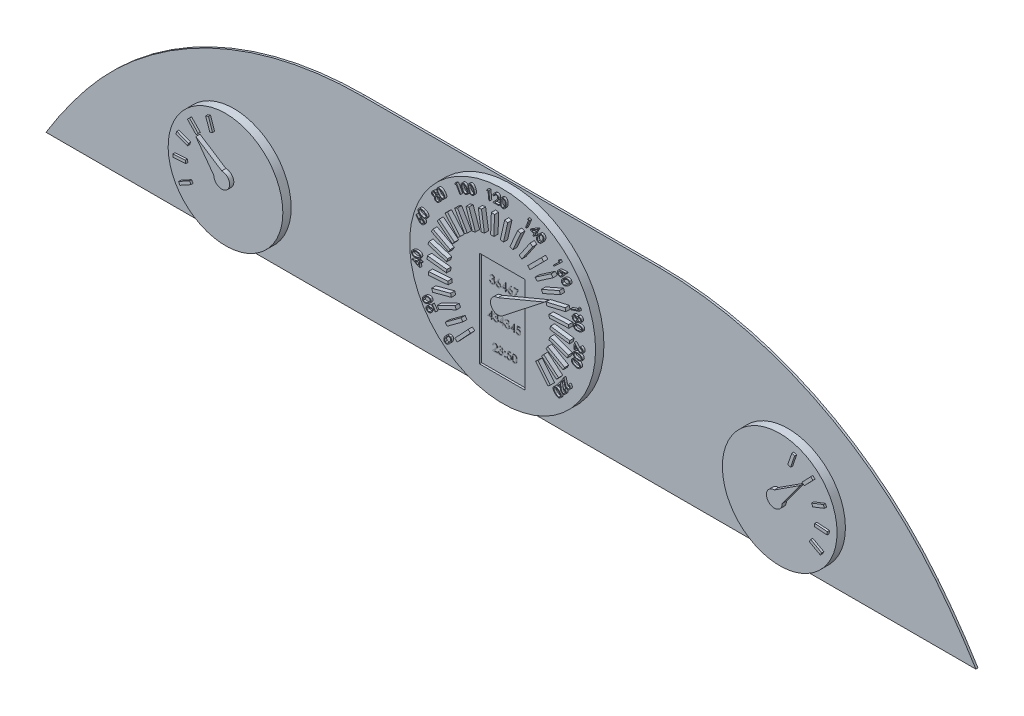
SolidWorks part; units mm, degrees
ref_plane "Front Plane" through (0, 0, 0) normal (0, 0, 1) x (1, 0, 0)
ref_plane "Top Plane" through (0, 0, 0) normal (0, 1, 0) x (1, 0, 0)
ref_plane "Right Plane" through (0, 0, 0) normal (1, 0, 0) x (0, 0, -1)
sketch "Sketch1" plane through (0, 0, 0) normal (0, 0, 1) x (1, 0, 0)
  line L1 (199.1432, -963.9827) -> (678.9972, -963.9827)
  line L2 (199.1432, -963.9827) -> (199.1432, -873.2403)
  line L3 (199.1432, -873.2403) -> (678.9972, -873.2403)
  line L4 (678.9972, -963.9827) -> (678.9972, -873.2403)
extrude "Boss-Extrude1" add sketch "Sketch1" along normal blind 1 contours L3 L4 L1 L2
sketch "Sketch2" plane through (0, 0, 1) normal (0, 0, 1) x (1, 0, 0)
  line L0 (439.0702, -790.2911) -> (439.0702, -1065.0749) construction
  circle A0 centre (439.0702, -918.6115) radius 44.5361
  circle A1 centre (571.7856, -936.6046) radius 27.4658
  circle A2 centre (306.3549, -936.6046) radius 27.4658
  point P6 (571.7856, -936.6046)
extrude "Boss-Extrude2" add sketch "Sketch2" along normal blind 4
sketch "Sketch3" plane through (0, 0, 5) normal (0, 0, 1) x (1, 0, 0)
  line L0 (424.5856, -938.6214) -> (425.708, -939.669)
  line L1 (424.5856, -938.6214) -> (418.2025, -945.4605)
  line L2 (425.708, -939.669) -> (419.3249, -946.5081)
  line L3 (418.2025, -945.4605) -> (419.3249, -946.5081)
  line L4 (421.1246, -935.5866) -> (422.0331, -936.8242)
  line L5 (422.0331, -936.8242) -> (414.4919, -942.3603)
  line L6 (421.1246, -935.5866) -> (413.5834, -941.1227)
  line L7 (413.5834, -941.1227) -> (414.4919, -942.3603)
  line L8 (418.2867, -931.9624) -> (418.9498, -933.3471)
  line L9 (418.9498, -933.3471) -> (410.5124, -937.3878)
  line L10 (418.2867, -931.9624) -> (409.8493, -936.0031)
  line L11 (409.8493, -936.0031) -> (410.5124, -937.3878)
  line L12 (416.1705, -927.8745) -> (416.5652, -929.3582)
  line L13 (416.5652, -929.3582) -> (407.5246, -931.7634)
  line L14 (416.1705, -927.8745) -> (407.1299, -930.2797)
  line L15 (407.1299, -930.2797) -> (407.5246, -931.7634)
  line L16 (414.8495, -923.465) -> (414.9621, -924.9961)
  line L17 (414.9621, -924.9961) -> (405.6322, -925.6822)
  line L18 (414.8495, -923.465) -> (405.5196, -924.1511)
  line L19 (405.5196, -924.1511) -> (405.6322, -925.6822)
  line L20 (414.3695, -918.8869) -> (414.1961, -920.4124)
  line L21 (414.1961, -920.4124) -> (404.9009, -919.3555)
  line L22 (414.3695, -918.8869) -> (405.0743, -917.8301)
  line L23 (405.0743, -917.8301) -> (404.9009, -919.3555)
  line L24 (414.7473, -914.2993) -> (414.2938, -915.7661)
  line L25 (414.2938, -915.7661) -> (405.3561, -913.003)
  line L26 (414.7473, -914.2993) -> (405.8096, -911.5362)
  line L27 (405.8096, -911.5362) -> (405.3561, -913.003)
  line L28 (415.9696, -909.8614) -> (415.2519, -911.2186)
  line L29 (415.2519, -911.2186) -> (406.982, -906.8453)
  line L30 (415.9696, -909.8614) -> (407.6997, -905.4881)
  line L31 (407.6997, -905.4881) -> (406.982, -906.8453)
  line L32 (417.9942, -905.7274) -> (417.0371, -906.9278)
  line L33 (417.0371, -906.9278) -> (409.7222, -901.0961)
  line L34 (417.9942, -905.7274) -> (410.6793, -899.8956)
  line L35 (410.6793, -899.8956) -> (409.7222, -901.0961)
  line L36 (420.7505, -902.0407) -> (419.5873, -903.0428)
  line L37 (419.5873, -903.0428) -> (413.4815, -895.9551)
  line L38 (420.7505, -902.0407) -> (414.6446, -894.953)
  line L39 (414.6446, -894.953) -> (413.4815, -895.9551)
  line L40 (424.1431, -898.9295) -> (422.8141, -899.6983)
  line L41 (422.8141, -899.6983) -> (418.1293, -891.6009)
  line L42 (424.1431, -898.9295) -> (419.4582, -890.832)
  line L43 (419.4582, -890.832) -> (418.1293, -891.6009)
  line L44 (428.0539, -896.5017) -> (426.6054, -897.0107)
  line L45 (426.6054, -897.0107) -> (423.5043, -888.1846)
  line L46 (428.0539, -896.5017) -> (424.9528, -887.6756)
  line L47 (424.9528, -887.6756) -> (423.5043, -888.1846)
  line L48 (432.3473, -894.8417) -> (430.8296, -895.073)
  line L49 (430.8296, -895.073) -> (429.4198, -885.8248)
  line L50 (432.3473, -894.8417) -> (430.9376, -885.5935)
  line L51 (430.9376, -885.5935) -> (429.4198, -885.8248)
  line L52 (436.8742, -894.0071) -> (435.3398, -893.9528)
  line L53 (435.3398, -893.9528) -> (435.6704, -884.6036)
  line L54 (436.8742, -894.0071) -> (437.2048, -884.6578)
  line L55 (437.2048, -884.6578) -> (435.6704, -884.6036)
  line L56 (441.4773, -894.0268) -> (439.9796, -893.6888)
  line L57 (439.9796, -893.6888) -> (442.0391, -884.5633)
  line L58 (441.4773, -894.0268) -> (443.5367, -884.9012)
  line L59 (443.5367, -884.9012) -> (442.0391, -884.5633)
  line L60 (445.9968, -894.9002) -> (444.5879, -894.2903)
  line L61 (444.5879, -894.2903) -> (448.3047, -885.7052)
  line L62 (445.9968, -894.9002) -> (449.7136, -886.3152)
  line L63 (449.7136, -886.3152) -> (448.3047, -885.7052)
  line L64 (450.2758, -896.597) -> (449.0045, -895.7363)
  line L65 (449.0045, -895.7363) -> (454.2496, -887.9899)
  line L66 (450.2758, -896.597) -> (455.5209, -888.8507)
  line L67 (455.5209, -888.8507) -> (454.2496, -887.9899)
  line L68 (454.1657, -899.0583) -> (453.0762, -897.9766)
  line L69 (453.0762, -897.9766) -> (459.6674, -891.3378)
  line L70 (454.1657, -899.0583) -> (460.7569, -892.4196)
  line L71 (460.7569, -892.4196) -> (459.6674, -891.3378)
  line L72 (457.5314, -902.1985) -> (456.6615, -900.9334)
  line L73 (456.6615, -900.9334) -> (464.37, -895.6329)
  line L74 (457.5314, -902.1985) -> (465.2399, -896.8979)
  line L75 (465.2399, -896.8979) -> (464.37, -895.6329)
  line L76 (460.2561, -905.9087) -> (459.636, -904.5042)
  line L77 (459.636, -904.5042) -> (468.1941, -900.7258)
  line L78 (460.2561, -905.9087) -> (468.8142, -902.1303)
  line L79 (468.8142, -902.1303) -> (468.1941, -900.7258)
  line L80 (462.245, -910.0599) -> (461.8963, -908.5648)
  line L81 (461.8963, -908.5648) -> (471.0068, -906.4398)
  line L82 (462.245, -910.0599) -> (471.3556, -907.935)
  line L83 (471.3556, -907.935) -> (471.0068, -906.4398)
  line L84 (463.4293, -914.5081) -> (463.364, -912.9742)
  line L85 (463.364, -912.9742) -> (472.7106, -912.5765)
  line L86 (463.4293, -914.5081) -> (472.7759, -914.1104)
  line L87 (472.7759, -914.1104) -> (472.7106, -912.5765)
  line L88 (463.7677, -919.0988) -> (463.9881, -917.5794)
  line L89 (463.9881, -917.5794) -> (473.2462, -918.9228)
  line L90 (463.7677, -919.0988) -> (473.0258, -920.4421)
  line L91 (473.0258, -920.4421) -> (473.2462, -918.9228)
  line L92 (463.2485, -923.6726) -> (463.747, -922.2205)
  line L93 (463.747, -922.2205) -> (472.5951, -925.2582)
  line L94 (463.2485, -923.6726) -> (472.0966, -926.7103)
  line L95 (472.0966, -926.7103) -> (472.5951, -925.2582)
  line L96 (461.8897, -928.0706) -> (462.6489, -926.7362)
  line L97 (462.6489, -926.7362) -> (470.7799, -931.3628)
  line L98 (461.8897, -928.0706) -> (470.0206, -932.6972)
  line L99 (470.0206, -932.6972) -> (470.7799, -931.3628)
  line L100 (459.7385, -932.1402) -> (460.7321, -930.9698)
  line L101 (460.7321, -930.9698) -> (467.8635, -937.0247)
  line L102 (459.7385, -932.1402) -> (466.8698, -938.195)
  line L103 (466.8698, -938.195) -> (467.8635, -937.0247)
  line L104 (456.8696, -935.74) -> (458.0631, -934.7743)
  line L105 (458.0631, -934.7743) -> (463.9473, -942.0471)
  line L106 (456.8696, -935.74) -> (462.7537, -943.0128)
  line L107 (462.7537, -943.0128) -> (463.9473, -942.0471)
  point P111 (439.0702, -918.6115)
  dimension "D1" = 27
extrude "Boss-Extrude3" add sketch "Sketch3" along normal blind 2
sketch "Sketch4" plane through (0, 0, 5) normal (0, 0, 1) x (1, 0, 0)
  arc A0 (463.5393, -944.1852) -> (417.1173, -948.7149) centre (437.5452, -917.9274) ccw construction
  text T0 "0     20      40       60     80    100   120     140    160    180   200     220" font "Century Gothic" height in points 16
  point P4 (463.5393, -944.1852)
extrude "Boss-Extrude4" add sketch "Sketch4" along normal blind 1
sketch "Sketch5" plane through (0, 0, 5) normal (0, 0, 1) x (1, 0, 0)
  line L0 (438.8848, -980.8986) -> (438.8848, -899.2584) construction
  line L2 (449.7701, -952.2142) -> (427.9994, -952.2142)
  line L3 (449.7701, -952.2142) -> (449.7701, -906.3192)
  line L4 (449.7701, -906.3192) -> (427.9994, -906.3192)
  line L5 (427.9994, -952.2142) -> (427.9994, -906.3192)
extrude "Cut-Extrude1" cut sketch "Sketch5" against normal blind 1
sketch "Sketch6" plane through (0, 0, 4) normal (0, 0, 1) x (1, 0, 0)
  line L0 (429.8591, -916.9975) -> (447.8586, -916.9975) construction
  line L1 (430.4479, -931.8849) -> (447.3539, -931.8849) construction
  line L2 (430.4479, -944.5014) -> (447.8586, -944.5014) construction
  text T0 "36467" font "Century Gothic" height in points 14
  text T1 "434345"
  text T2 "23:50"
extrude "Boss-Extrude5" add sketch "Sketch6" along normal blind 0.09
sketch "Sketch8" plane through (0, 0, 5) normal (0, 0, 1) x (1, 0, 0)
  line L0 (290.8246, -945.9874) -> (290.1379, -944.7432)
  line L1 (290.8246, -945.9874) -> (285.5435, -948.902)
  line L2 (290.1379, -944.7432) -> (284.8568, -947.6578)
  line L3 (285.5435, -948.902) -> (284.8568, -947.6578)
  line L4 (288.3143, -938.5449) -> (288.2178, -937.1271)
  line L5 (288.3143, -938.5449) -> (282.2962, -938.9546)
  line L6 (288.2178, -937.1271) -> (282.1997, -937.5367)
  line L7 (282.2962, -938.9546) -> (282.1997, -937.5367)
  line L8 (289.1845, -930.7388) -> (289.6963, -929.413)
  line L9 (289.1845, -930.7388) -> (283.5572, -928.5668)
  line L10 (289.6963, -929.413) -> (284.0689, -927.241)
  line L11 (283.5572, -928.5668) -> (284.0689, -927.241)
  line L12 (293.2722, -924.0319) -> (294.2963, -923.0466)
  line L13 (293.2722, -924.0319) -> (289.0901, -919.6851)
  line L14 (294.2963, -923.0466) -> (290.1141, -918.6998)
  line L15 (289.0901, -919.6851) -> (290.1141, -918.6998)
  line L16 (299.8114, -919.6809) -> (301.1559, -919.2207)
  line L17 (299.8114, -919.6809) -> (297.8581, -913.9739)
  line L18 (301.1559, -919.2207) -> (299.2026, -913.5137)
  line L19 (297.8581, -913.9739) -> (299.2026, -913.5137)
  circle A0 centre (306.3549, -936.6046) radius 18.1446 construction
  point P26 (306.3549, -936.6046)
  dimension "D1" = 5
extrude "Boss-Extrude6" add sketch "Sketch8" along normal blind 1
sketch "Sketch9" plane through (0, 0, 5) normal (0, 0, 1) x (1, 0, 0)
  line L0 (302.7714, -935.6836) -> (294.1361, -923.8778)
  line L2 (294.1361, -923.8778) -> (306.5565, -931.8985)
  circle A0 centre (306.5565, -935.6836) radius 3.7851
  point P4 (293.7843, -923.5393)
  point P5 (294.1361, -923.8778)
  point P6 (0, 0)
  point P9 (0, 0)
  line M14 (294.2963, -923.0466) -> (293.2722, -924.0319)
  line M15 (293.2722, -924.0319) -> (289.0901, -919.6851)
extrude "Boss-Extrude7" add sketch "Sketch9" along normal blind 2 contours A0 | A0 L2 L0 M14 M15 region at (300.7775, -930.1337, 5) region at (306.5565, -935.6836, 5)
sketch "Sketch10" plane through (0, 0, 5) normal (0, 0, 1) x (1, 0, 0)
  line L0 (438.8848, -918.3299) -> (461.2255, -908.982)
  line L1 (461.2255, -908.982) -> (441.4525, -924.4665)
  arc A0 (438.8848, -918.3299) -> (441.4525, -924.4665) centre (438.8848, -921.9354) ccw
extrude "Boss-Extrude8" add sketch "Sketch10" along normal blind 2
ref_plane "Plane1" through (438.8848, -952.2142, 4) normal (1, 0, 0) x (0, 0, -1)
mirror "Mirror1" about plane through (438.8848, -952.2142, 4) normal (1, 0, 0) of "Boss-Extrude7", "Boss-Extrude6"
sketch "Sketch11" plane through (0, 0, 1) normal (0, 0, 1) x (1, 0, 0)
  circle A0 centre (439.0702, -1100.2598) radius 261.0669
  point P2 (438.7992, -1101.8861)
  point P3 (439.0702, -1100.2598)
extrude "Cut-Extrude-Thin1" cut sketch "Sketch11" against normal through all thin thin type one direction wall 100
fillet "Fillet1" radius 170 2 edges at (567.9812, -873.2403, 0.5) (310.1592, -873.2403, 0.5)
